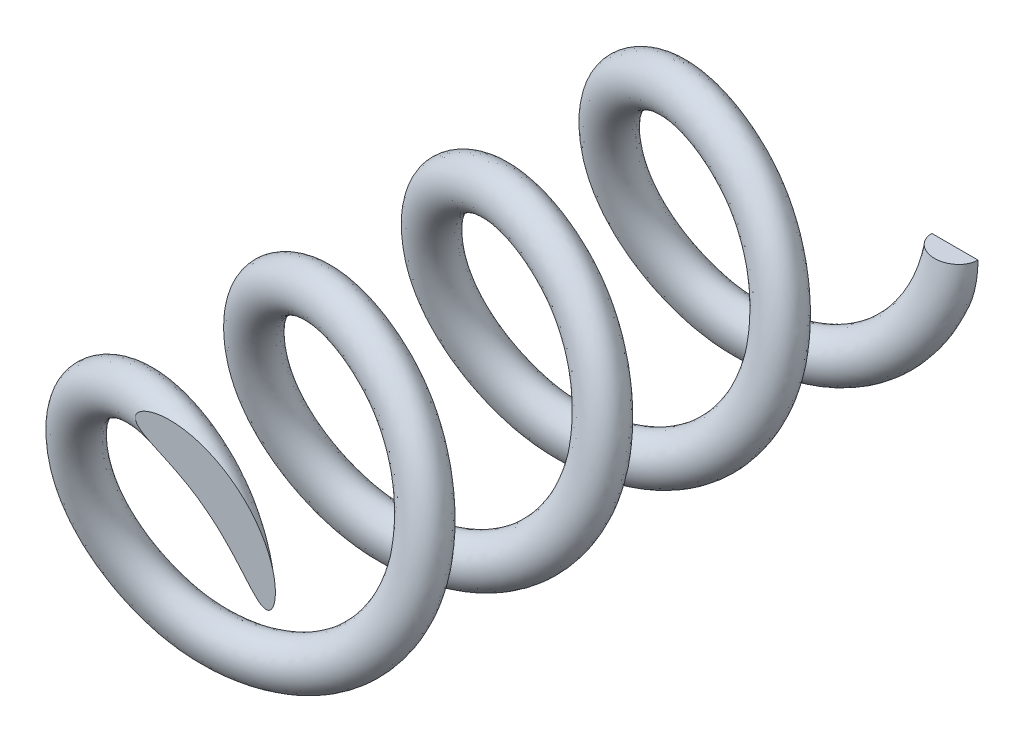
SolidWorks part; units mm, degrees
material "Alloy Steel"
ref_plane "Front Plane" through (0, 0, 0) normal (0, 0, 1) x (1, 0, 0)
ref_plane "Top Plane" through (0, 0, 0) normal (0, 1, 0) x (1, 0, 0)
ref_plane "Right Plane" through (0, 0, 0) normal (1, 0, 0) x (0, 0, -1)
sketch "Sketch1" plane through (0, 0, 0) normal (0, 0, 1) x (1, 0, 0)
  circle A0 centre (0, 0) radius 2.2
curve "Helix/Spiral1" pitch 3.5 height 14 radius 2.2 left hand yes centre (0, 0, 0) axis (0, 0, 1) start towards (1, 0, 0)
sketch "Sketch2" plane through (0, 0, 0) normal (0, 1, 0) x (1, 0, 0)
  line L0 (-2.2, 0) -> (2.2, 0) construction
  line L1 (-2.3495, 0) -> (2.3495, 0) construction
  circle A0 centre (2.2, 0) radius 0.4
  dimension "D1" = 2.2
sweep "Sweep1" add profiles "Sketch2" path "Helix/Spiral1"
sketch "Sketch4" plane through (0, 0, 0) normal (1, 0, 0) x (0, 0, -1)
  line L1 (0, 4) -> (1.27, 4)
  line L2 (0, 4) -> (0, -4)
  line L3 (0, -4) -> (1.27, -4)
  line L4 (1.27, 4) -> (1.27, -4)
  line L5 (-4, 4) -> (-5.6068, 4)
  line L6 (-4, 4) -> (-4, -4)
  line L7 (-4, -4) -> (-5.6068, -4)
  line L8 (-5.6068, 4) -> (-5.6068, -4)
  dimension "D1" = 4
extrude "Cut-Extrude1" [suppressed] cut sketch "Sketch4" against normal through all and the other way through all
sketch "Sketch5" plane through (0, 0, 0) normal (0, 1, 0) x (-1, 0, 0)
  line L1 (2.3495, 0) -> (-3.3033, 0)
  line L2 (2.3495, 0) -> (2.3495, -1.27)
  line L3 (2.3495, -1.27) -> (-3.3033, -1.27)
  line L4 (-3.3033, 0) -> (-3.3033, -1.27)
  line L5 (2.3495, 13.4887) -> (-3.0134, 13.4887)
  line L6 (2.3495, 13.4887) -> (2.3495, 14.7571)
  line L7 (2.3495, 14.7571) -> (-3.0134, 14.7571)
  line L8 (-3.0134, 13.4887) -> (-3.0134, 14.7571)
extrude "Cut-Extrude2" cut sketch "Sketch5" against normal through all and the other way through all
scale "Scale1" scale about centroid uniform scaling no x scale factor 1 y scale factor 1 z scale factor 0.88
ref_axis "Axis1" through (0, 0, -0.1875) along (0, 0, 1)
